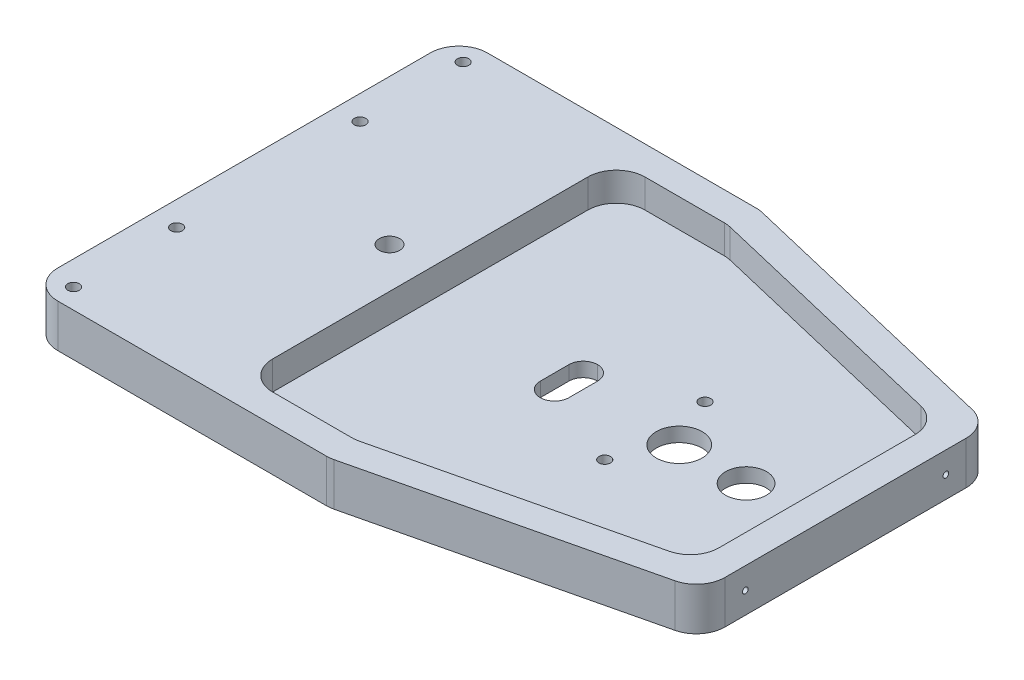
SolidWorks part; units mm, degrees
material "Carvalho"
ref_plane "Plano frontal" through (0, 0, 0) normal (0, 0, 1) x (1, 0, 0)
ref_plane "Plano superior" through (0, 0, 0) normal (0, 1, 0) x (1, 0, 0)
ref_plane "Plano direito" through (0, 0, 0) normal (1, 0, 0) x (0, 0, -1)
sketch "Esboço1" plane through (0, 0, 0) normal (0, 1, 0) x (1, 0, 0)
  line L0 (210, 50) -> (105, 75)
  line L1 (0, -75) -> (105, -75)
  line L2 (0, -75) -> (0, 75)
  line L3 (0, 75) -> (105, 75)
  line L4 (210, -50) -> (210, 50)
  line L7 (105, -75) -> (210, -50)
  line L8 (-14.8259, 0) -> (14.392, 0) construction
  line L9 (0, 21.2472) -> (0, -16.7598) construction
  circle A0 centre (50.8, 0) radius 3.5719
  circle A1 centre (175.26, 0) radius 7.14
  circle A2 centre (151.92, 0) radius 8
  circle A3 centre (151.92, 0) radius 8 construction
  circle A4 centre (8.5, -68) radius 2
  circle A5 centre (8.5, -32) radius 2
  circle A6 centre (8.5, -68) radius 2 construction
  circle A7 centre (8.5, -32) radius 2 construction
  circle A8 centre (8.5, 32) radius 2
  circle A9 centre (8.5, 68) radius 2
  point P0 (0, 0)
  dimension "D3" = 7.1437
  dimension "D5" = 14.28
  dimension "D1" = 25
  dimension "D2" = 150
  dimension "D4" = 50.8
  dimension "D6" = 210
  dimension "D7" = 175.26
  dimension "D8" = 105
extrude "Ressalto-extrusão1" add sketch "Esboço1" along normal blind 15
sketch "Esboço2" plane through (210, 0, 0) normal (1, 0, 0) x (0, 0, -1)
  line L0 (0, 15) -> (0, 0) construction
  line L1 (-50, 15) -> (50, 15) construction
  circle A0 centre (35, 7.5) radius 1
  circle A1 centre (-35, 7.5) radius 1
  point P9 (0, 7.5)
  dimension "D1" = 2
  dimension "D2" = 35
extrude "Corte-extrusão1" cut sketch "Esboço2" against normal blind 10
sketch "Esboço3" plane through (0, 15, 0) normal (0, 1, 0) x (1, 0, 0)
  line L0 (200, 42.1014) -> (200, -42.1014)
  line L2 (65, -65) -> (65, 65)
  line L6 (210, -50) -> (210, 50) construction
  line L7 (0, 75) -> (0, -75) construction
  line L8 (-22.821, 0) -> (224.4652, 0) construction
  line L9 (65, 65) -> (103.8259, 65)
  line L10 (103.8259, 65) -> (200, 42.1014)
  line L11 (65, -65) -> (103.8259, -65)
  line L12 (103.8259, -65) -> (200, -42.1014)
  line L13 (105, -75) -> (210, -50) construction
  line L14 (0, -75) -> (105, -75) construction
  dimension "D1" = 10
  dimension "D2" = 65
  dimension "D3" = 10
  dimension "D4" = 10
extrude "Corte-extrusão2" cut sketch "Esboço3" against normal blind 10
fillet "Filete1" radius 10 12 edges at (105, 7.5, 75) (0, 7.5, 75) (0, 7.5, -75) (210, 7.5, 50) (105, 7.5, -75) (210, 7.5, -50) (200, 10, 42.1014) (200, 10, -42.1014) (103.8259, 10, 65) (65, 10, 65) (103.8259, 10, -65) (65, 10, -65)
sketch "Esboço5" plane through (0, 0, 0) normal (0, -1, 0) x (1, 0, 0)
  line L0 (175.26, 0) -> (113.42, 0) construction
  line L2 (143.42, 17.5) -> (143.42, -17.5) construction
  line L3 (175.26, 0) -> (101.1849, 0) construction
  line L8 (108.42, -10) -> (118.42, -10)
  line L9 (108.42, -10) -> (108.42, 10)
  line L10 (108.42, 10) -> (118.42, 10)
  line L11 (118.42, -10) -> (118.42, 10)
  line L12 (108.42, -10) -> (118.42, 10) construction
  line L13 (108.42, 10) -> (118.42, -10) construction
  circle A0 centre (143.42, 17.5) radius 2
  circle A1 centre (143.42, -17.5) radius 2
  point P5 (143.42, 0)
  point P13 (0, 0)
  dimension "D6" = 4
  dimension "D1" = 35
  dimension "D2" = 25
  dimension "D3" = 10
  dimension "D4" = 31.84
  dimension "D5" = 20
extrude "Corte-extrusão4" cut sketch "Esboço5" against normal through all
fillet "Filete2" radius 5 4 edges at (108.42, 2.5, -10) (108.42, 2.5, 10) (118.42, 2.5, 10) (118.42, 2.5, -10)
